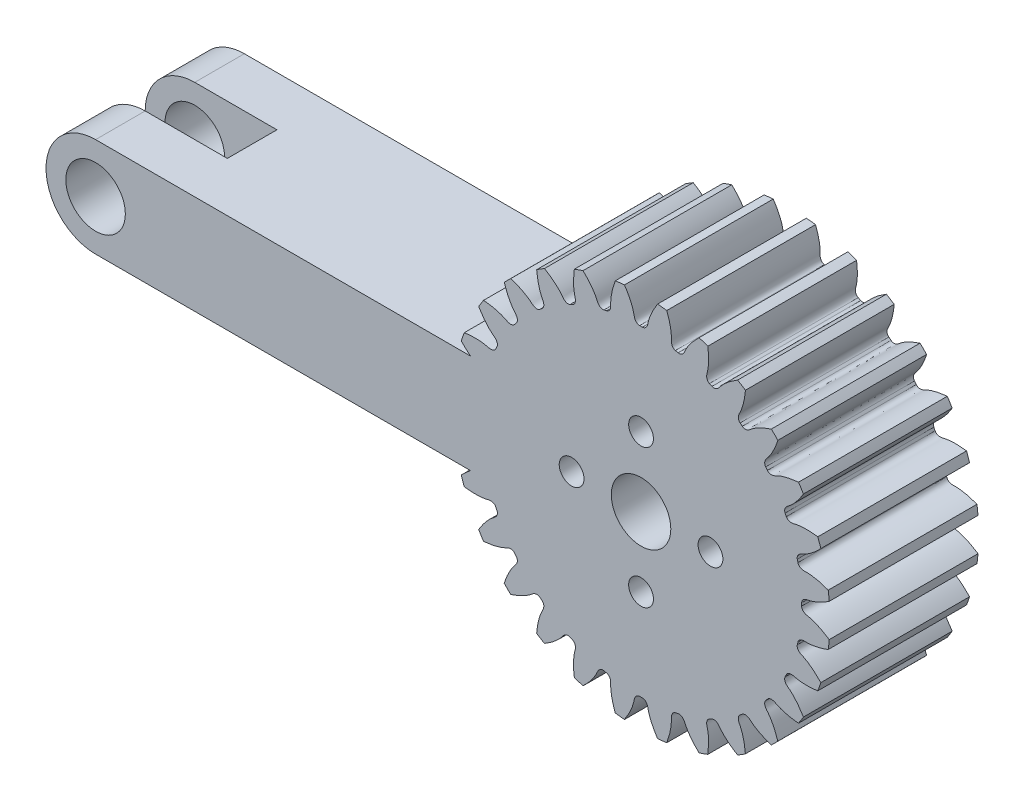
SolidWorks part; units mm, degrees
ref_plane "前视基准面" through (0, 0, 0) normal (0, 0, 1) x (1, 0, 0)
ref_plane "上视基准面" through (0, 0, 0) normal (0, 1, 0) x (1, 0, 0)
ref_plane "右视基准面" through (0, 0, 0) normal (1, 0, 0) x (0, 0, -1)
other "Configuration Table"
sketch "草图1" plane through (0, 0, 0) normal (0, 0, 1) x (1, 0, 0)
  line L4 (-55, -5) -> (-17.1897, -5)
  line L5 (-17.1897, 5) -> (-55, 5)
  circle A0 centre (0, 0) radius 3
  circle A1 centre (-55, 0) radius 3
  arc A104 (-18.1289, -5.8518) -> (-17.8223, -6.7281) centre (0, 0) ccw
  arc A105 (-14.6488, -6.9) -> (-14.528, -7.1508) centre (0, 0) ccw
  arc A106 (-16.3722, -9.7392) -> (-15.8784, -10.5252) centre (0, 0) ccw
  arc A107 (-12.7461, -9.9866) -> (-12.5725, -10.2043) centre (0, 0) ccw
  arc A108 (-13.7946, -13.1382) -> (-13.1382, -13.7946) centre (0, 0) ccw
  arc A109 (-10.2043, -12.5725) -> (-9.9866, -12.7461) centre (0, 0) ccw
  arc A110 (-10.5252, -15.8784) -> (-9.7392, -16.3722) centre (0, 0) ccw
  arc A111 (-7.1508, -14.528) -> (-6.9, -14.6488) centre (0, 0) ccw
  arc A112 (-6.7281, -17.8223) -> (-5.8518, -18.1289) centre (0, 0) ccw
  arc A113 (-3.7388, -15.755) -> (-3.4673, -15.8169) centre (0, 0) ccw
  arc A114 (-2.5935, -18.8726) -> (-1.6711, -18.9766) centre (0, 0) ccw
  arc A115 (-0.1392, -16.1919) -> (0.1392, -16.1919) centre (0, 0) ccw
  arc A116 (1.6711, -18.9766) -> (2.5935, -18.8726) centre (0, 0) ccw
  arc A117 (3.4673, -15.8169) -> (3.7388, -15.755) centre (0, 0) ccw
  arc A118 (5.8518, -18.1289) -> (6.7281, -17.8223) centre (0, 0) ccw
  arc A119 (6.9, -14.6488) -> (7.1508, -14.528) centre (0, 0) ccw
  arc A120 (9.7392, -16.3722) -> (10.5252, -15.8784) centre (0, 0) ccw
  arc A121 (9.9866, -12.7461) -> (10.2043, -12.5725) centre (0, 0) ccw
  arc A122 (13.1382, -13.7946) -> (13.7946, -13.1382) centre (0, 0) ccw
  arc A123 (12.5725, -10.2043) -> (12.7461, -9.9866) centre (0, 0) ccw
  arc A124 (15.8784, -10.5252) -> (16.3722, -9.7392) centre (0, 0) ccw
  arc A125 (14.528, -7.1508) -> (14.6488, -6.9) centre (0, 0) ccw
  arc A126 (17.8223, -6.7281) -> (18.1289, -5.8518) centre (0, 0) ccw
  arc A127 (15.755, -3.7388) -> (15.8169, -3.4673) centre (0, 0) ccw
  arc A128 (18.8726, -2.5935) -> (18.9766, -1.6711) centre (0, 0) ccw
  arc A129 (16.1919, -0.1392) -> (16.1919, 0.1392) centre (0, 0) ccw
  arc A130 (18.9766, 1.6711) -> (18.8726, 2.5935) centre (0, 0) ccw
  arc A131 (15.8169, 3.4673) -> (15.755, 3.7388) centre (0, 0) ccw
  arc A132 (18.1289, 5.8518) -> (17.8223, 6.7281) centre (0, 0) ccw
  arc A133 (14.6488, 6.9) -> (14.528, 7.1508) centre (0, 0) ccw
  arc A134 (16.3722, 9.7392) -> (15.8784, 10.5252) centre (0, 0) ccw
  arc A135 (12.7461, 9.9866) -> (12.5725, 10.2043) centre (0, 0) ccw
  arc A136 (13.7946, 13.1382) -> (13.1382, 13.7946) centre (0, 0) ccw
  arc A137 (10.2043, 12.5725) -> (9.9866, 12.7461) centre (0, 0) ccw
  arc A138 (10.5252, 15.8784) -> (9.7392, 16.3722) centre (0, 0) ccw
  arc A139 (7.1508, 14.528) -> (6.9, 14.6488) centre (0, 0) ccw
  arc A140 (6.7281, 17.8223) -> (5.8518, 18.1289) centre (0, 0) ccw
  arc A141 (3.7388, 15.755) -> (3.4673, 15.8169) centre (0, 0) ccw
  arc A142 (2.5935, 18.8726) -> (1.6711, 18.9766) centre (0, 0) ccw
  arc A143 (0.1392, 16.1919) -> (-0.1392, 16.1919) centre (0, 0) ccw
  arc A144 (-1.6711, 18.9766) -> (-2.5935, 18.8726) centre (0, 0) ccw
  arc A145 (-3.4673, 15.8169) -> (-3.7388, 15.755) centre (0, 0) ccw
  arc A146 (-5.8518, 18.1289) -> (-6.7281, 17.8223) centre (0, 0) ccw
  arc A147 (-6.9, 14.6488) -> (-7.1508, 14.528) centre (0, 0) ccw
  arc A148 (-9.7392, 16.3722) -> (-10.5252, 15.8784) centre (0, 0) ccw
  arc A149 (-9.9866, 12.7461) -> (-10.2043, 12.5725) centre (0, 0) ccw
  arc A150 (-13.1382, 13.7946) -> (-13.7946, 13.1382) centre (0, 0) ccw
  arc A151 (-12.5725, 10.2043) -> (-12.7461, 9.9866) centre (0, 0) ccw
  arc A152 (-15.8784, 10.5252) -> (-16.3722, 9.7392) centre (0, 0) ccw
  arc A153 (-14.528, 7.1508) -> (-14.6488, 6.9) centre (0, 0) ccw
  arc A154 (-17.8223, 6.7281) -> (-18.1289, 5.8518) centre (0, 0) ccw
  arc A155 (-55, 5) -> (-55, -5) centre (-55, 0) ccw
  spline S104 degree 3 poles (-17.1897, -5) (-17.2348, -5.0343) (-17.3497, -5.1242) (-17.5362, -5.2798) (-17.8086, -5.525) (-18.005, -5.7208) (-18.1289, -5.8518) knots 0.59534 0.59534 0.59534 0.59534 0.645252 0.723706 0.808982 0.967655 0.967655 0.967655 0.967655
  spline S105 degree 3 poles (-17.8223, -6.7281) (-17.6438, -6.7532) (-17.3681, -6.7839) (-17.0023, -6.8057) (-16.7348, -6.8117) (-16.4906, -6.808) (-16.2698, -6.7965) (-16.0729, -6.7788) (-15.8998, -6.7568) (-15.7506, -6.7322) (-15.6252, -6.7066) (-15.5335, -6.6846) (-15.4713, -6.6672) (-15.4305, -6.6561) (-15.3936, -6.6472) (-15.3338, -6.6343) (-15.2507, -6.6212) (-15.1426, -6.6153) (-15.0302, -6.6239) (-14.9083, -6.6553) (-14.7624, -6.7338) (-14.6816, -6.8327) (-14.6488, -6.9) knots 0.032345 0.032345 0.032345 0.032345 0.191018 0.276294 0.354748 0.42638 0.49119 0.549178 0.600343 0.644687 0.682208 0.712908 0.727669 0.739016 0.750139 0.761058 0.792861 0.824038 0.856152 0.891705 0.934026 1 1 1 1
  spline S106 degree 3 poles (-14.528, -7.1508) (-14.4959, -7.2184) (-14.4689, -7.3433) (-14.4985, -7.5063) (-14.5499, -7.6211) (-14.6133, -7.7144) (-14.6854, -7.7952) (-14.7474, -7.852) (-14.7948, -7.8908) (-14.8247, -7.9141) (-14.8589, -7.939) (-14.9112, -7.9768) (-14.9856, -8.0348) (-15.0838, -8.1169) (-15.1961, -8.2182) (-15.3212, -8.3398) (-15.4578, -8.4827) (-15.6044, -8.6481) (-15.7595, -8.8368) (-15.9217, -9.0496) (-16.1327, -9.3492) (-16.2806, -9.5839) (-16.3722, -9.7392) knots 0 0 0 0 0.065974 0.108295 0.143848 0.175962 0.207139 0.238942 0.249861 0.260984 0.272331 0.287092 0.317792 0.355313 0.399657 0.450822 0.50881 0.57362 0.645252 0.723706 0.808982 0.967655 0.967655 0.967655 0.967655
  spline S107 degree 3 poles (-15.8784, -10.5252) (-15.6987, -10.51) (-15.4231, -10.4786) (-15.0616, -10.4184) (-14.7995, -10.3647) (-14.5622, -10.3068) (-14.3496, -10.2465) (-14.1615, -10.1854) (-13.9976, -10.1255) (-13.8577, -10.0683) (-13.7411, -10.0154) (-13.6566, -9.9735) (-13.5998, -9.9428) (-13.5625, -9.9228) (-13.5285, -9.9059) (-13.4731, -9.8801) (-13.395, -9.8488) (-13.2909, -9.819) (-13.1794, -9.8023) (-13.0536, -9.8058) (-12.8939, -9.8499) (-12.7931, -9.9284) (-12.7461, -9.9866) knots 0.032345 0.032345 0.032345 0.032345 0.191018 0.276294 0.354748 0.42638 0.49119 0.549178 0.600343 0.644687 0.682208 0.712908 0.727669 0.739016 0.750139 0.761058 0.792861 0.824038 0.856152 0.891705 0.934026 1 1 1 1
  spline S108 degree 3 poles (-12.5725, -10.2043) (-12.5262, -10.2631) (-12.4721, -10.3788) (-12.4647, -10.5443) (-12.4893, -10.6677) (-12.5303, -10.7727) (-12.5826, -10.8676) (-12.6304, -10.9367) (-12.668, -10.9851) (-12.692, -11.0145) (-12.7197, -11.0464) (-12.7623, -11.0949) (-12.822, -11.168) (-12.8994, -11.2698) (-12.9864, -11.3936) (-13.0813, -11.5399) (-13.1826, -11.7097) (-13.2888, -11.9036) (-13.3981, -12.1221) (-13.5087, -12.3656) (-13.6478, -12.7047) (-13.7398, -12.9664) (-13.7946, -13.1382) knots 0 0 0 0 0.065974 0.108295 0.143848 0.175962 0.207139 0.238942 0.249861 0.260984 0.272331 0.287092 0.317792 0.355313 0.399657 0.450822 0.50881 0.57362 0.645252 0.723706 0.808982 0.967655 0.967655 0.967655 0.967655
  spline S109 degree 3 poles (-13.1382, -13.7946) (-12.9664, -13.7398) (-12.7047, -13.6478) (-12.3656, -13.5087) (-12.1221, -13.3981) (-11.9036, -13.2888) (-11.7097, -13.1826) (-11.5399, -13.0813) (-11.3936, -12.9864) (-11.2698, -12.8994) (-11.168, -12.822) (-11.0949, -12.7623) (-11.0464, -12.7197) (-11.0145, -12.692) (-10.9851, -12.668) (-10.9367, -12.6304) (-10.8676, -12.5826) (-10.7727, -12.5303) (-10.6677, -12.4893) (-10.5443, -12.4647) (-10.3788, -12.4721) (-10.2631, -12.5262) (-10.2043, -12.5725) knots 0.032345 0.032345 0.032345 0.032345 0.191018 0.276294 0.354748 0.42638 0.49119 0.549178 0.600343 0.644687 0.682208 0.712908 0.727669 0.739016 0.750139 0.761058 0.792861 0.824038 0.856152 0.891705 0.934026 1 1 1 1
  spline S110 degree 3 poles (-9.9866, -12.7461) (-9.9284, -12.7931) (-9.8499, -12.8939) (-9.8058, -13.0536) (-9.8023, -13.1794) (-9.819, -13.2909) (-9.8488, -13.395) (-9.8801, -13.4731) (-9.9059, -13.5285) (-9.9228, -13.5625) (-9.9428, -13.5998) (-9.9735, -13.6566) (-10.0154, -13.7411) (-10.0683, -13.8577) (-10.1255, -13.9976) (-10.1854, -14.1615) (-10.2465, -14.3496) (-10.3068, -14.5622) (-10.3647, -14.7995) (-10.4184, -15.0616) (-10.4786, -15.4231) (-10.51, -15.6987) (-10.5252, -15.8784) knots 0 0 0 0 0.065974 0.108295 0.143848 0.175962 0.207139 0.238942 0.249861 0.260984 0.272331 0.287092 0.317792 0.355313 0.399657 0.450822 0.50881 0.57362 0.645252 0.723706 0.808982 0.967655 0.967655 0.967655 0.967655
  spline S111 degree 3 poles (-9.7392, -16.3722) (-9.5839, -16.2806) (-9.3492, -16.1327) (-9.0496, -15.9217) (-8.8368, -15.7595) (-8.6481, -15.6044) (-8.4827, -15.4578) (-8.3398, -15.3212) (-8.2182, -15.1961) (-8.1169, -15.0838) (-8.0348, -14.9856) (-7.9768, -14.9112) (-7.939, -14.8589) (-7.9141, -14.8247) (-7.8908, -14.7948) (-7.852, -14.7474) (-7.7952, -14.6854) (-7.7144, -14.6133) (-7.6211, -14.5499) (-7.5063, -14.4985) (-7.3433, -14.4689) (-7.2184, -14.4959) (-7.1508, -14.528) knots 0.032345 0.032345 0.032345 0.032345 0.191018 0.276294 0.354748 0.42638 0.49119 0.549178 0.600343 0.644687 0.682208 0.712908 0.727669 0.739016 0.750139 0.761058 0.792861 0.824038 0.856152 0.891705 0.934026 1 1 1 1
  spline S112 degree 3 poles (-6.9, -14.6488) (-6.8327, -14.6816) (-6.7338, -14.7624) (-6.6553, -14.9083) (-6.6239, -15.0302) (-6.6153, -15.1426) (-6.6212, -15.2507) (-6.6343, -15.3338) (-6.6472, -15.3936) (-6.6561, -15.4305) (-6.6672, -15.4713) (-6.6846, -15.5335) (-6.7066, -15.6252) (-6.7322, -15.7506) (-6.7568, -15.8998) (-6.7788, -16.0729) (-6.7965, -16.2698) (-6.808, -16.4906) (-6.8117, -16.7348) (-6.8057, -17.0023) (-6.7839, -17.3681) (-6.7532, -17.6438) (-6.7281, -17.8223) knots 0 0 0 0 0.065974 0.108295 0.143848 0.175962 0.207139 0.238942 0.249861 0.260984 0.272331 0.287092 0.317792 0.355313 0.399657 0.450822 0.50881 0.57362 0.645252 0.723706 0.808982 0.967655 0.967655 0.967655 0.967655
  spline S113 degree 3 poles (-5.8518, -18.1289) (-5.7208, -18.005) (-5.525, -17.8086) (-5.2798, -17.5362) (-5.1084, -17.3308) (-4.959, -17.1376) (-4.8304, -16.9578) (-4.7214, -16.7928) (-4.6307, -16.6438) (-4.5569, -16.5118) (-4.4987, -16.3978) (-4.4588, -16.3124) (-4.4336, -16.2529) (-4.4168, -16.2141) (-4.4008, -16.1797) (-4.3735, -16.1249) (-4.332, -16.0518) (-4.2692, -15.9635) (-4.1924, -15.881) (-4.0919, -15.8053) (-3.9395, -15.7401) (-3.8118, -15.7387) (-3.7388, -15.755) knots 0.032345 0.032345 0.032345 0.032345 0.191018 0.276294 0.354748 0.42638 0.49119 0.549178 0.600343 0.644687 0.682208 0.712908 0.727669 0.739016 0.750139 0.761058 0.792861 0.824038 0.856152 0.891705 0.934026 1 1 1 1
  spline S114 degree 3 poles (-3.4673, -15.8169) (-3.3945, -15.8339) (-3.28, -15.8907) (-3.171, -16.0155) (-3.1133, -16.1273) (-3.0799, -16.235) (-3.0616, -16.3417) (-3.0559, -16.4256) (-3.0551, -16.4868) (-3.0556, -16.5248) (-3.0574, -16.567) (-3.0604, -16.6315) (-3.0615, -16.7259) (-3.0586, -16.8538) (-3.0494, -17.0047) (-3.0323, -17.1783) (-3.0057, -17.3743) (-2.9678, -17.592) (-2.917, -17.831) (-2.8517, -18.0904) (-2.749, -18.4422) (-2.6578, -18.7041) (-2.5935, -18.8726) knots 0 0 0 0 0.065974 0.108295 0.143848 0.175962 0.207139 0.238942 0.249861 0.260984 0.272331 0.287092 0.317792 0.355313 0.399657 0.450822 0.50881 0.57362 0.645252 0.723706 0.808982 0.967655 0.967655 0.967655 0.967655
  spline S115 degree 3 poles (-1.6711, -18.9766) (-1.5709, -18.8266) (-1.4237, -18.5915) (-1.2453, -18.2714) (-1.1239, -18.033) (-1.0212, -17.8114) (-0.9358, -17.6075) (-0.8662, -17.4224) (-0.811, -17.2569) (-0.7684, -17.1118) (-0.7371, -16.9878) (-0.7172, -16.8956) (-0.7058, -16.832) (-0.6981, -16.7904) (-0.6901, -16.7533) (-0.6758, -16.6938) (-0.6515, -16.6133) (-0.6099, -16.5133) (-0.5534, -16.4157) (-0.4723, -16.3196) (-0.3383, -16.2221) (-0.214, -16.1923) (-0.1392, -16.1919) knots 0.032345 0.032345 0.032345 0.032345 0.191018 0.276294 0.354748 0.42638 0.49119 0.549178 0.600343 0.644687 0.682208 0.712908 0.727669 0.739016 0.750139 0.761058 0.792861 0.824038 0.856152 0.891705 0.934026 1 1 1 1
  spline S116 degree 3 poles (0.1392, -16.1919) (0.214, -16.1923) (0.3383, -16.2221) (0.4723, -16.3196) (0.5534, -16.4157) (0.6099, -16.5133) (0.6515, -16.6133) (0.6758, -16.6938) (0.6901, -16.7533) (0.6981, -16.7904) (0.7058, -16.832) (0.7172, -16.8956) (0.7371, -16.9878) (0.7684, -17.1118) (0.811, -17.2569) (0.8662, -17.4224) (0.9358, -17.6075) (1.0212, -17.8114) (1.1239, -18.033) (1.2453, -18.2714) (1.4237, -18.5915) (1.5709, -18.8266) (1.6711, -18.9766) knots 0 0 0 0 0.065974 0.108295 0.143848 0.175962 0.207139 0.238942 0.249861 0.260984 0.272331 0.287092 0.317792 0.355313 0.399657 0.450822 0.50881 0.57362 0.645252 0.723706 0.808982 0.967655 0.967655 0.967655 0.967655
  spline S117 degree 3 poles (2.5935, -18.8726) (2.6578, -18.7041) (2.749, -18.4422) (2.8517, -18.0904) (2.917, -17.831) (2.9678, -17.592) (3.0057, -17.3743) (3.0323, -17.1783) (3.0494, -17.0047) (3.0586, -16.8538) (3.0615, -16.7259) (3.0604, -16.6315) (3.0574, -16.567) (3.0556, -16.5248) (3.0551, -16.4868) (3.0559, -16.4256) (3.0616, -16.3417) (3.0799, -16.235) (3.1133, -16.1273) (3.171, -16.0155) (3.28, -15.8907) (3.3945, -15.8339) (3.4673, -15.8169) knots 0.032345 0.032345 0.032345 0.032345 0.191018 0.276294 0.354748 0.42638 0.49119 0.549178 0.600343 0.644687 0.682208 0.712908 0.727669 0.739016 0.750139 0.761058 0.792861 0.824038 0.856152 0.891705 0.934026 1 1 1 1
  spline S118 degree 3 poles (3.7388, -15.755) (3.8118, -15.7387) (3.9395, -15.7401) (4.0919, -15.8053) (4.1924, -15.881) (4.2692, -15.9635) (4.332, -16.0518) (4.3735, -16.1249) (4.4008, -16.1797) (4.4168, -16.2141) (4.4336, -16.2529) (4.4588, -16.3124) (4.4987, -16.3978) (4.5569, -16.5118) (4.6307, -16.6438) (4.7214, -16.7928) (4.8304, -16.9578) (4.959, -17.1376) (5.1084, -17.3308) (5.2798, -17.5362) (5.525, -17.8086) (5.7208, -18.005) (5.8518, -18.1289) knots 0 0 0 0 0.065974 0.108295 0.143848 0.175962 0.207139 0.238942 0.249861 0.260984 0.272331 0.287092 0.317792 0.355313 0.399657 0.450822 0.50881 0.57362 0.645252 0.723706 0.808982 0.967655 0.967655 0.967655 0.967655
  spline S119 degree 3 poles (6.7281, -17.8223) (6.7532, -17.6438) (6.7839, -17.3681) (6.8057, -17.0023) (6.8117, -16.7348) (6.808, -16.4906) (6.7965, -16.2698) (6.7788, -16.0729) (6.7568, -15.8998) (6.7322, -15.7506) (6.7066, -15.6252) (6.6846, -15.5335) (6.6672, -15.4713) (6.6561, -15.4305) (6.6472, -15.3936) (6.6343, -15.3338) (6.6212, -15.2507) (6.6153, -15.1426) (6.6239, -15.0302) (6.6553, -14.9083) (6.7338, -14.7624) (6.8327, -14.6816) (6.9, -14.6488) knots 0.032345 0.032345 0.032345 0.032345 0.191018 0.276294 0.354748 0.42638 0.49119 0.549178 0.600343 0.644687 0.682208 0.712908 0.727669 0.739016 0.750139 0.761058 0.792861 0.824038 0.856152 0.891705 0.934026 1 1 1 1
  spline S120 degree 3 poles (7.1508, -14.528) (7.2184, -14.4959) (7.3433, -14.4689) (7.5063, -14.4985) (7.6211, -14.5499) (7.7144, -14.6133) (7.7952, -14.6854) (7.852, -14.7474) (7.8908, -14.7948) (7.9141, -14.8247) (7.939, -14.8589) (7.9768, -14.9112) (8.0348, -14.9856) (8.1169, -15.0838) (8.2182, -15.1961) (8.3398, -15.3212) (8.4827, -15.4578) (8.6481, -15.6044) (8.8368, -15.7595) (9.0496, -15.9217) (9.3492, -16.1327) (9.5839, -16.2806) (9.7392, -16.3722) knots 0 0 0 0 0.065974 0.108295 0.143848 0.175962 0.207139 0.238942 0.249861 0.260984 0.272331 0.287092 0.317792 0.355313 0.399657 0.450822 0.50881 0.57362 0.645252 0.723706 0.808982 0.967655 0.967655 0.967655 0.967655
  spline S121 degree 3 poles (10.5252, -15.8784) (10.51, -15.6987) (10.4786, -15.4231) (10.4184, -15.0616) (10.3647, -14.7995) (10.3068, -14.5622) (10.2465, -14.3496) (10.1854, -14.1615) (10.1255, -13.9976) (10.0683, -13.8577) (10.0154, -13.7411) (9.9735, -13.6566) (9.9428, -13.5998) (9.9228, -13.5625) (9.9059, -13.5285) (9.8801, -13.4731) (9.8488, -13.395) (9.819, -13.2909) (9.8023, -13.1794) (9.8058, -13.0536) (9.8499, -12.8939) (9.9284, -12.7931) (9.9866, -12.7461) knots 0.032345 0.032345 0.032345 0.032345 0.191018 0.276294 0.354748 0.42638 0.49119 0.549178 0.600343 0.644687 0.682208 0.712908 0.727669 0.739016 0.750139 0.761058 0.792861 0.824038 0.856152 0.891705 0.934026 1 1 1 1
  spline S122 degree 3 poles (10.2043, -12.5725) (10.2631, -12.5262) (10.3788, -12.4721) (10.5443, -12.4647) (10.6677, -12.4893) (10.7727, -12.5303) (10.8676, -12.5826) (10.9367, -12.6304) (10.9851, -12.668) (11.0145, -12.692) (11.0464, -12.7197) (11.0949, -12.7623) (11.168, -12.822) (11.2698, -12.8994) (11.3936, -12.9864) (11.5399, -13.0813) (11.7097, -13.1826) (11.9036, -13.2888) (12.1221, -13.3981) (12.3656, -13.5087) (12.7047, -13.6478) (12.9664, -13.7398) (13.1382, -13.7946) knots 0 0 0 0 0.065974 0.108295 0.143848 0.175962 0.207139 0.238942 0.249861 0.260984 0.272331 0.287092 0.317792 0.355313 0.399657 0.450822 0.50881 0.57362 0.645252 0.723706 0.808982 0.967655 0.967655 0.967655 0.967655
  spline S123 degree 3 poles (13.7946, -13.1382) (13.7398, -12.9664) (13.6478, -12.7047) (13.5087, -12.3656) (13.3981, -12.1221) (13.2888, -11.9036) (13.1826, -11.7097) (13.0813, -11.5399) (12.9864, -11.3936) (12.8994, -11.2698) (12.822, -11.168) (12.7623, -11.0949) (12.7197, -11.0464) (12.692, -11.0145) (12.668, -10.9851) (12.6304, -10.9367) (12.5826, -10.8676) (12.5303, -10.7727) (12.4893, -10.6677) (12.4647, -10.5443) (12.4721, -10.3788) (12.5262, -10.2631) (12.5725, -10.2043) knots 0.032345 0.032345 0.032345 0.032345 0.191018 0.276294 0.354748 0.42638 0.49119 0.549178 0.600343 0.644687 0.682208 0.712908 0.727669 0.739016 0.750139 0.761058 0.792861 0.824038 0.856152 0.891705 0.934026 1 1 1 1
  spline S124 degree 3 poles (12.7461, -9.9866) (12.7931, -9.9284) (12.8939, -9.8499) (13.0536, -9.8058) (13.1794, -9.8023) (13.2909, -9.819) (13.395, -9.8488) (13.4731, -9.8801) (13.5285, -9.9059) (13.5625, -9.9228) (13.5998, -9.9428) (13.6566, -9.9735) (13.7411, -10.0154) (13.8577, -10.0683) (13.9976, -10.1255) (14.1615, -10.1854) (14.3496, -10.2465) (14.5622, -10.3068) (14.7995, -10.3647) (15.0616, -10.4184) (15.4231, -10.4786) (15.6987, -10.51) (15.8784, -10.5252) knots 0 0 0 0 0.065974 0.108295 0.143848 0.175962 0.207139 0.238942 0.249861 0.260984 0.272331 0.287092 0.317792 0.355313 0.399657 0.450822 0.50881 0.57362 0.645252 0.723706 0.808982 0.967655 0.967655 0.967655 0.967655
  spline S125 degree 3 poles (16.3722, -9.7392) (16.2806, -9.5839) (16.1327, -9.3492) (15.9217, -9.0496) (15.7595, -8.8368) (15.6044, -8.6481) (15.4578, -8.4827) (15.3212, -8.3398) (15.1961, -8.2182) (15.0838, -8.1169) (14.9856, -8.0348) (14.9112, -7.9768) (14.8589, -7.939) (14.8247, -7.9141) (14.7948, -7.8908) (14.7474, -7.852) (14.6854, -7.7952) (14.6133, -7.7144) (14.5499, -7.6211) (14.4985, -7.5063) (14.4689, -7.3433) (14.4959, -7.2184) (14.528, -7.1508) knots 0.032345 0.032345 0.032345 0.032345 0.191018 0.276294 0.354748 0.42638 0.49119 0.549178 0.600343 0.644687 0.682208 0.712908 0.727669 0.739016 0.750139 0.761058 0.792861 0.824038 0.856152 0.891705 0.934026 1 1 1 1
  spline S126 degree 3 poles (14.6488, -6.9) (14.6816, -6.8327) (14.7624, -6.7338) (14.9083, -6.6553) (15.0302, -6.6239) (15.1426, -6.6153) (15.2507, -6.6212) (15.3338, -6.6343) (15.3936, -6.6472) (15.4305, -6.6561) (15.4713, -6.6672) (15.5335, -6.6846) (15.6252, -6.7066) (15.7506, -6.7322) (15.8998, -6.7568) (16.0729, -6.7788) (16.2698, -6.7965) (16.4906, -6.808) (16.7348, -6.8117) (17.0023, -6.8057) (17.3681, -6.7839) (17.6438, -6.7532) (17.8223, -6.7281) knots 0 0 0 0 0.065974 0.108295 0.143848 0.175962 0.207139 0.238942 0.249861 0.260984 0.272331 0.287092 0.317792 0.355313 0.399657 0.450822 0.50881 0.57362 0.645252 0.723706 0.808982 0.967655 0.967655 0.967655 0.967655
  spline S127 degree 3 poles (18.1289, -5.8518) (18.005, -5.7208) (17.8086, -5.525) (17.5362, -5.2798) (17.3308, -5.1084) (17.1376, -4.959) (16.9578, -4.8304) (16.7928, -4.7214) (16.6438, -4.6307) (16.5118, -4.5569) (16.3978, -4.4987) (16.3124, -4.4588) (16.2529, -4.4336) (16.2141, -4.4168) (16.1797, -4.4008) (16.1249, -4.3735) (16.0518, -4.332) (15.9635, -4.2692) (15.881, -4.1924) (15.8053, -4.0919) (15.7401, -3.9395) (15.7387, -3.8118) (15.755, -3.7388) knots 0.032345 0.032345 0.032345 0.032345 0.191018 0.276294 0.354748 0.42638 0.49119 0.549178 0.600343 0.644687 0.682208 0.712908 0.727669 0.739016 0.750139 0.761058 0.792861 0.824038 0.856152 0.891705 0.934026 1 1 1 1
  spline S128 degree 3 poles (15.8169, -3.4673) (15.8339, -3.3945) (15.8907, -3.28) (16.0155, -3.171) (16.1273, -3.1133) (16.235, -3.0799) (16.3417, -3.0616) (16.4256, -3.0559) (16.4868, -3.0551) (16.5248, -3.0556) (16.567, -3.0574) (16.6315, -3.0604) (16.7259, -3.0615) (16.8538, -3.0586) (17.0047, -3.0494) (17.1783, -3.0323) (17.3743, -3.0057) (17.592, -2.9678) (17.831, -2.917) (18.0904, -2.8517) (18.4422, -2.749) (18.7041, -2.6578) (18.8726, -2.5935) knots 0 0 0 0 0.065974 0.108295 0.143848 0.175962 0.207139 0.238942 0.249861 0.260984 0.272331 0.287092 0.317792 0.355313 0.399657 0.450822 0.50881 0.57362 0.645252 0.723706 0.808982 0.967655 0.967655 0.967655 0.967655
  spline S129 degree 3 poles (18.9766, -1.6711) (18.8266, -1.5709) (18.5915, -1.4237) (18.2714, -1.2453) (18.033, -1.1239) (17.8114, -1.0212) (17.6075, -0.9358) (17.4224, -0.8662) (17.2569, -0.811) (17.1118, -0.7684) (16.9878, -0.7371) (16.8956, -0.7172) (16.832, -0.7058) (16.7904, -0.6981) (16.7533, -0.6901) (16.6938, -0.6758) (16.6133, -0.6515) (16.5133, -0.6099) (16.4157, -0.5534) (16.3196, -0.4723) (16.2221, -0.3383) (16.1923, -0.214) (16.1919, -0.1392) knots 0.032345 0.032345 0.032345 0.032345 0.191018 0.276294 0.354748 0.42638 0.49119 0.549178 0.600343 0.644687 0.682208 0.712908 0.727669 0.739016 0.750139 0.761058 0.792861 0.824038 0.856152 0.891705 0.934026 1 1 1 1
  spline S130 degree 3 poles (16.1919, 0.1392) (16.1923, 0.214) (16.2221, 0.3383) (16.3196, 0.4723) (16.4157, 0.5534) (16.5133, 0.6099) (16.6133, 0.6515) (16.6938, 0.6758) (16.7533, 0.6901) (16.7904, 0.6981) (16.832, 0.7058) (16.8956, 0.7172) (16.9878, 0.7371) (17.1118, 0.7684) (17.2569, 0.811) (17.4224, 0.8662) (17.6075, 0.9358) (17.8114, 1.0212) (18.033, 1.1239) (18.2714, 1.2453) (18.5915, 1.4237) (18.8266, 1.5709) (18.9766, 1.6711) knots 0 0 0 0 0.065974 0.108295 0.143848 0.175962 0.207139 0.238942 0.249861 0.260984 0.272331 0.287092 0.317792 0.355313 0.399657 0.450822 0.50881 0.57362 0.645252 0.723706 0.808982 0.967655 0.967655 0.967655 0.967655
  spline S131 degree 3 poles (18.8726, 2.5935) (18.7041, 2.6578) (18.4422, 2.749) (18.0904, 2.8517) (17.831, 2.917) (17.592, 2.9678) (17.3743, 3.0057) (17.1783, 3.0323) (17.0047, 3.0494) (16.8538, 3.0586) (16.7259, 3.0615) (16.6315, 3.0604) (16.567, 3.0574) (16.5248, 3.0556) (16.4868, 3.0551) (16.4256, 3.0559) (16.3417, 3.0616) (16.235, 3.0799) (16.1273, 3.1133) (16.0155, 3.171) (15.8907, 3.28) (15.8339, 3.3945) (15.8169, 3.4673) knots 0.032345 0.032345 0.032345 0.032345 0.191018 0.276294 0.354748 0.42638 0.49119 0.549178 0.600343 0.644687 0.682208 0.712908 0.727669 0.739016 0.750139 0.761058 0.792861 0.824038 0.856152 0.891705 0.934026 1 1 1 1
  spline S132 degree 3 poles (15.755, 3.7388) (15.7387, 3.8118) (15.7401, 3.9395) (15.8053, 4.0919) (15.881, 4.1924) (15.9635, 4.2692) (16.0518, 4.332) (16.1249, 4.3735) (16.1797, 4.4008) (16.2141, 4.4168) (16.2529, 4.4336) (16.3124, 4.4588) (16.3978, 4.4987) (16.5118, 4.5569) (16.6438, 4.6307) (16.7928, 4.7214) (16.9578, 4.8304) (17.1376, 4.959) (17.3308, 5.1084) (17.5362, 5.2798) (17.8086, 5.525) (18.005, 5.7208) (18.1289, 5.8518) knots 0 0 0 0 0.065974 0.108295 0.143848 0.175962 0.207139 0.238942 0.249861 0.260984 0.272331 0.287092 0.317792 0.355313 0.399657 0.450822 0.50881 0.57362 0.645252 0.723706 0.808982 0.967655 0.967655 0.967655 0.967655
  spline S133 degree 3 poles (17.8223, 6.7281) (17.6438, 6.7532) (17.3681, 6.7839) (17.0023, 6.8057) (16.7348, 6.8117) (16.4906, 6.808) (16.2698, 6.7965) (16.0729, 6.7788) (15.8998, 6.7568) (15.7506, 6.7322) (15.6252, 6.7066) (15.5335, 6.6846) (15.4713, 6.6672) (15.4305, 6.6561) (15.3936, 6.6472) (15.3338, 6.6343) (15.2507, 6.6212) (15.1426, 6.6153) (15.0302, 6.6239) (14.9083, 6.6553) (14.7624, 6.7338) (14.6816, 6.8327) (14.6488, 6.9) knots 0.032345 0.032345 0.032345 0.032345 0.191018 0.276294 0.354748 0.42638 0.49119 0.549178 0.600343 0.644687 0.682208 0.712908 0.727669 0.739016 0.750139 0.761058 0.792861 0.824038 0.856152 0.891705 0.934026 1 1 1 1
  spline S134 degree 3 poles (14.528, 7.1508) (14.4959, 7.2184) (14.4689, 7.3433) (14.4985, 7.5063) (14.5499, 7.6211) (14.6133, 7.7144) (14.6854, 7.7952) (14.7474, 7.852) (14.7948, 7.8908) (14.8247, 7.9141) (14.8589, 7.939) (14.9112, 7.9768) (14.9856, 8.0348) (15.0838, 8.1169) (15.1961, 8.2182) (15.3212, 8.3398) (15.4578, 8.4827) (15.6044, 8.6481) (15.7595, 8.8368) (15.9217, 9.0496) (16.1327, 9.3492) (16.2806, 9.5839) (16.3722, 9.7392) knots 0 0 0 0 0.065974 0.108295 0.143848 0.175962 0.207139 0.238942 0.249861 0.260984 0.272331 0.287092 0.317792 0.355313 0.399657 0.450822 0.50881 0.57362 0.645252 0.723706 0.808982 0.967655 0.967655 0.967655 0.967655
  spline S135 degree 3 poles (15.8784, 10.5252) (15.6987, 10.51) (15.4231, 10.4786) (15.0616, 10.4184) (14.7995, 10.3647) (14.5622, 10.3068) (14.3496, 10.2465) (14.1615, 10.1854) (13.9976, 10.1255) (13.8577, 10.0683) (13.7411, 10.0154) (13.6566, 9.9735) (13.5998, 9.9428) (13.5625, 9.9228) (13.5285, 9.9059) (13.4731, 9.8801) (13.395, 9.8488) (13.2909, 9.819) (13.1794, 9.8023) (13.0536, 9.8058) (12.8939, 9.8499) (12.7931, 9.9284) (12.7461, 9.9866) knots 0.032345 0.032345 0.032345 0.032345 0.191018 0.276294 0.354748 0.42638 0.49119 0.549178 0.600343 0.644687 0.682208 0.712908 0.727669 0.739016 0.750139 0.761058 0.792861 0.824038 0.856152 0.891705 0.934026 1 1 1 1
  spline S136 degree 3 poles (12.5725, 10.2043) (12.5262, 10.2631) (12.4721, 10.3788) (12.4647, 10.5443) (12.4893, 10.6677) (12.5303, 10.7727) (12.5826, 10.8676) (12.6304, 10.9367) (12.668, 10.9851) (12.692, 11.0145) (12.7197, 11.0464) (12.7623, 11.0949) (12.822, 11.168) (12.8994, 11.2698) (12.9864, 11.3936) (13.0813, 11.5399) (13.1826, 11.7097) (13.2888, 11.9036) (13.3981, 12.1221) (13.5087, 12.3656) (13.6478, 12.7047) (13.7398, 12.9664) (13.7946, 13.1382) knots 0 0 0 0 0.065974 0.108295 0.143848 0.175962 0.207139 0.238942 0.249861 0.260984 0.272331 0.287092 0.317792 0.355313 0.399657 0.450822 0.50881 0.57362 0.645252 0.723706 0.808982 0.967655 0.967655 0.967655 0.967655
  spline S137 degree 3 poles (13.1382, 13.7946) (12.9664, 13.7398) (12.7047, 13.6478) (12.3656, 13.5087) (12.1221, 13.3981) (11.9036, 13.2888) (11.7097, 13.1826) (11.5399, 13.0813) (11.3936, 12.9864) (11.2698, 12.8994) (11.168, 12.822) (11.0949, 12.7623) (11.0464, 12.7197) (11.0145, 12.692) (10.9851, 12.668) (10.9367, 12.6304) (10.8676, 12.5826) (10.7727, 12.5303) (10.6677, 12.4893) (10.5443, 12.4647) (10.3788, 12.4721) (10.2631, 12.5262) (10.2043, 12.5725) knots 0.032345 0.032345 0.032345 0.032345 0.191018 0.276294 0.354748 0.42638 0.49119 0.549178 0.600343 0.644687 0.682208 0.712908 0.727669 0.739016 0.750139 0.761058 0.792861 0.824038 0.856152 0.891705 0.934026 1 1 1 1
  spline S138 degree 3 poles (9.9866, 12.7461) (9.9284, 12.7931) (9.8499, 12.8939) (9.8058, 13.0536) (9.8023, 13.1794) (9.819, 13.2909) (9.8488, 13.395) (9.8801, 13.4731) (9.9059, 13.5285) (9.9228, 13.5625) (9.9428, 13.5998) (9.9735, 13.6566) (10.0154, 13.7411) (10.0683, 13.8577) (10.1255, 13.9976) (10.1854, 14.1615) (10.2465, 14.3496) (10.3068, 14.5622) (10.3647, 14.7995) (10.4184, 15.0616) (10.4786, 15.4231) (10.51, 15.6987) (10.5252, 15.8784) knots 0 0 0 0 0.065974 0.108295 0.143848 0.175962 0.207139 0.238942 0.249861 0.260984 0.272331 0.287092 0.317792 0.355313 0.399657 0.450822 0.50881 0.57362 0.645252 0.723706 0.808982 0.967655 0.967655 0.967655 0.967655
  spline S139 degree 3 poles (9.7392, 16.3722) (9.5839, 16.2806) (9.3492, 16.1327) (9.0496, 15.9217) (8.8368, 15.7595) (8.6481, 15.6044) (8.4827, 15.4578) (8.3398, 15.3212) (8.2182, 15.1961) (8.1169, 15.0838) (8.0348, 14.9856) (7.9768, 14.9112) (7.939, 14.8589) (7.9141, 14.8247) (7.8908, 14.7948) (7.852, 14.7474) (7.7952, 14.6854) (7.7144, 14.6133) (7.6211, 14.5499) (7.5063, 14.4985) (7.3433, 14.4689) (7.2184, 14.4959) (7.1508, 14.528) knots 0.032345 0.032345 0.032345 0.032345 0.191018 0.276294 0.354748 0.42638 0.49119 0.549178 0.600343 0.644687 0.682208 0.712908 0.727669 0.739016 0.750139 0.761058 0.792861 0.824038 0.856152 0.891705 0.934026 1 1 1 1
  spline S140 degree 3 poles (6.9, 14.6488) (6.8327, 14.6816) (6.7338, 14.7624) (6.6553, 14.9083) (6.6239, 15.0302) (6.6153, 15.1426) (6.6212, 15.2507) (6.6343, 15.3338) (6.6472, 15.3936) (6.6561, 15.4305) (6.6672, 15.4713) (6.6846, 15.5335) (6.7066, 15.6252) (6.7322, 15.7506) (6.7568, 15.8998) (6.7788, 16.0729) (6.7965, 16.2698) (6.808, 16.4906) (6.8117, 16.7348) (6.8057, 17.0023) (6.7839, 17.3681) (6.7532, 17.6438) (6.7281, 17.8223) knots 0 0 0 0 0.065974 0.108295 0.143848 0.175962 0.207139 0.238942 0.249861 0.260984 0.272331 0.287092 0.317792 0.355313 0.399657 0.450822 0.50881 0.57362 0.645252 0.723706 0.808982 0.967655 0.967655 0.967655 0.967655
  spline S141 degree 3 poles (5.8518, 18.1289) (5.7208, 18.005) (5.525, 17.8086) (5.2798, 17.5362) (5.1084, 17.3308) (4.959, 17.1376) (4.8304, 16.9578) (4.7214, 16.7928) (4.6307, 16.6438) (4.5569, 16.5118) (4.4987, 16.3978) (4.4588, 16.3124) (4.4336, 16.2529) (4.4168, 16.2141) (4.4008, 16.1797) (4.3735, 16.1249) (4.332, 16.0518) (4.2692, 15.9635) (4.1924, 15.881) (4.0919, 15.8053) (3.9395, 15.7401) (3.8118, 15.7387) (3.7388, 15.755) knots 0.032345 0.032345 0.032345 0.032345 0.191018 0.276294 0.354748 0.42638 0.49119 0.549178 0.600343 0.644687 0.682208 0.712908 0.727669 0.739016 0.750139 0.761058 0.792861 0.824038 0.856152 0.891705 0.934026 1 1 1 1
  spline S142 degree 3 poles (3.4673, 15.8169) (3.3945, 15.8339) (3.28, 15.8907) (3.171, 16.0155) (3.1133, 16.1273) (3.0799, 16.235) (3.0616, 16.3417) (3.0559, 16.4256) (3.0551, 16.4868) (3.0556, 16.5248) (3.0574, 16.567) (3.0604, 16.6315) (3.0615, 16.7259) (3.0586, 16.8538) (3.0494, 17.0047) (3.0323, 17.1783) (3.0057, 17.3743) (2.9678, 17.592) (2.917, 17.831) (2.8517, 18.0904) (2.749, 18.4422) (2.6578, 18.7041) (2.5935, 18.8726) knots 0 0 0 0 0.065974 0.108295 0.143848 0.175962 0.207139 0.238942 0.249861 0.260984 0.272331 0.287092 0.317792 0.355313 0.399657 0.450822 0.50881 0.57362 0.645252 0.723706 0.808982 0.967655 0.967655 0.967655 0.967655
  spline S143 degree 3 poles (1.6711, 18.9766) (1.5709, 18.8266) (1.4237, 18.5915) (1.2453, 18.2714) (1.1239, 18.033) (1.0212, 17.8114) (0.9358, 17.6075) (0.8662, 17.4224) (0.811, 17.2569) (0.7684, 17.1118) (0.7371, 16.9878) (0.7172, 16.8956) (0.7058, 16.832) (0.6981, 16.7904) (0.6901, 16.7533) (0.6758, 16.6938) (0.6515, 16.6133) (0.6099, 16.5133) (0.5534, 16.4157) (0.4723, 16.3196) (0.3383, 16.2221) (0.214, 16.1923) (0.1392, 16.1919) knots 0.032345 0.032345 0.032345 0.032345 0.191018 0.276294 0.354748 0.42638 0.49119 0.549178 0.600343 0.644687 0.682208 0.712908 0.727669 0.739016 0.750139 0.761058 0.792861 0.824038 0.856152 0.891705 0.934026 1 1 1 1
  spline S144 degree 3 poles (-0.1392, 16.1919) (-0.214, 16.1923) (-0.3383, 16.2221) (-0.4723, 16.3196) (-0.5534, 16.4157) (-0.6099, 16.5133) (-0.6515, 16.6133) (-0.6758, 16.6938) (-0.6901, 16.7533) (-0.6981, 16.7904) (-0.7058, 16.832) (-0.7172, 16.8956) (-0.7371, 16.9878) (-0.7684, 17.1118) (-0.811, 17.2569) (-0.8662, 17.4224) (-0.9358, 17.6075) (-1.0212, 17.8114) (-1.1239, 18.033) (-1.2453, 18.2714) (-1.4237, 18.5915) (-1.5709, 18.8266) (-1.6711, 18.9766) knots 0 0 0 0 0.065974 0.108295 0.143848 0.175962 0.207139 0.238942 0.249861 0.260984 0.272331 0.287092 0.317792 0.355313 0.399657 0.450822 0.50881 0.57362 0.645252 0.723706 0.808982 0.967655 0.967655 0.967655 0.967655
  spline S145 degree 3 poles (-2.5935, 18.8726) (-2.6578, 18.7041) (-2.749, 18.4422) (-2.8517, 18.0904) (-2.917, 17.831) (-2.9678, 17.592) (-3.0057, 17.3743) (-3.0323, 17.1783) (-3.0494, 17.0047) (-3.0586, 16.8538) (-3.0615, 16.7259) (-3.0604, 16.6315) (-3.0574, 16.567) (-3.0556, 16.5248) (-3.0551, 16.4868) (-3.0559, 16.4256) (-3.0616, 16.3417) (-3.0799, 16.235) (-3.1133, 16.1273) (-3.171, 16.0155) (-3.28, 15.8907) (-3.3945, 15.8339) (-3.4673, 15.8169) knots 0.032345 0.032345 0.032345 0.032345 0.191018 0.276294 0.354748 0.42638 0.49119 0.549178 0.600343 0.644687 0.682208 0.712908 0.727669 0.739016 0.750139 0.761058 0.792861 0.824038 0.856152 0.891705 0.934026 1 1 1 1
  spline S146 degree 3 poles (-3.7388, 15.755) (-3.8118, 15.7387) (-3.9395, 15.7401) (-4.0919, 15.8053) (-4.1924, 15.881) (-4.2692, 15.9635) (-4.332, 16.0518) (-4.3735, 16.1249) (-4.4008, 16.1797) (-4.4168, 16.2141) (-4.4336, 16.2529) (-4.4588, 16.3124) (-4.4987, 16.3978) (-4.5569, 16.5118) (-4.6307, 16.6438) (-4.7214, 16.7928) (-4.8304, 16.9578) (-4.959, 17.1376) (-5.1084, 17.3308) (-5.2798, 17.5362) (-5.525, 17.8086) (-5.7208, 18.005) (-5.8518, 18.1289) knots 0 0 0 0 0.065974 0.108295 0.143848 0.175962 0.207139 0.238942 0.249861 0.260984 0.272331 0.287092 0.317792 0.355313 0.399657 0.450822 0.50881 0.57362 0.645252 0.723706 0.808982 0.967655 0.967655 0.967655 0.967655
  spline S147 degree 3 poles (-6.7281, 17.8223) (-6.7532, 17.6438) (-6.7839, 17.3681) (-6.8057, 17.0023) (-6.8117, 16.7348) (-6.808, 16.4906) (-6.7965, 16.2698) (-6.7788, 16.0729) (-6.7568, 15.8998) (-6.7322, 15.7506) (-6.7066, 15.6252) (-6.6846, 15.5335) (-6.6672, 15.4713) (-6.6561, 15.4305) (-6.6472, 15.3936) (-6.6343, 15.3338) (-6.6212, 15.2507) (-6.6153, 15.1426) (-6.6239, 15.0302) (-6.6553, 14.9083) (-6.7338, 14.7624) (-6.8327, 14.6816) (-6.9, 14.6488) knots 0.032345 0.032345 0.032345 0.032345 0.191018 0.276294 0.354748 0.42638 0.49119 0.549178 0.600343 0.644687 0.682208 0.712908 0.727669 0.739016 0.750139 0.761058 0.792861 0.824038 0.856152 0.891705 0.934026 1 1 1 1
  spline S148 degree 3 poles (-7.1508, 14.528) (-7.2184, 14.4959) (-7.3433, 14.4689) (-7.5063, 14.4985) (-7.6211, 14.5499) (-7.7144, 14.6133) (-7.7952, 14.6854) (-7.852, 14.7474) (-7.8908, 14.7948) (-7.9141, 14.8247) (-7.939, 14.8589) (-7.9768, 14.9112) (-8.0348, 14.9856) (-8.1169, 15.0838) (-8.2182, 15.1961) (-8.3398, 15.3212) (-8.4827, 15.4578) (-8.6481, 15.6044) (-8.8368, 15.7595) (-9.0496, 15.9217) (-9.3492, 16.1327) (-9.5839, 16.2806) (-9.7392, 16.3722) knots 0 0 0 0 0.065974 0.108295 0.143848 0.175962 0.207139 0.238942 0.249861 0.260984 0.272331 0.287092 0.317792 0.355313 0.399657 0.450822 0.50881 0.57362 0.645252 0.723706 0.808982 0.967655 0.967655 0.967655 0.967655
  spline S149 degree 3 poles (-10.5252, 15.8784) (-10.51, 15.6987) (-10.4786, 15.4231) (-10.4184, 15.0616) (-10.3647, 14.7995) (-10.3068, 14.5622) (-10.2465, 14.3496) (-10.1854, 14.1615) (-10.1255, 13.9976) (-10.0683, 13.8577) (-10.0154, 13.7411) (-9.9735, 13.6566) (-9.9428, 13.5998) (-9.9228, 13.5625) (-9.9059, 13.5285) (-9.8801, 13.4731) (-9.8488, 13.395) (-9.819, 13.2909) (-9.8023, 13.1794) (-9.8058, 13.0536) (-9.8499, 12.8939) (-9.9284, 12.7931) (-9.9866, 12.7461) knots 0.032345 0.032345 0.032345 0.032345 0.191018 0.276294 0.354748 0.42638 0.49119 0.549178 0.600343 0.644687 0.682208 0.712908 0.727669 0.739016 0.750139 0.761058 0.792861 0.824038 0.856152 0.891705 0.934026 1 1 1 1
  spline S150 degree 3 poles (-10.2043, 12.5725) (-10.2631, 12.5262) (-10.3788, 12.4721) (-10.5443, 12.4647) (-10.6677, 12.4893) (-10.7727, 12.5303) (-10.8676, 12.5826) (-10.9367, 12.6304) (-10.9851, 12.668) (-11.0145, 12.692) (-11.0464, 12.7197) (-11.0949, 12.7623) (-11.168, 12.822) (-11.2698, 12.8994) (-11.3936, 12.9864) (-11.5399, 13.0813) (-11.7097, 13.1826) (-11.9036, 13.2888) (-12.1221, 13.3981) (-12.3656, 13.5087) (-12.7047, 13.6478) (-12.9664, 13.7398) (-13.1382, 13.7946) knots 0 0 0 0 0.065974 0.108295 0.143848 0.175962 0.207139 0.238942 0.249861 0.260984 0.272331 0.287092 0.317792 0.355313 0.399657 0.450822 0.50881 0.57362 0.645252 0.723706 0.808982 0.967655 0.967655 0.967655 0.967655
  spline S151 degree 3 poles (-13.7946, 13.1382) (-13.7398, 12.9664) (-13.6478, 12.7047) (-13.5087, 12.3656) (-13.3981, 12.1221) (-13.2888, 11.9036) (-13.1826, 11.7097) (-13.0813, 11.5399) (-12.9864, 11.3936) (-12.8994, 11.2698) (-12.822, 11.168) (-12.7623, 11.0949) (-12.7197, 11.0464) (-12.692, 11.0145) (-12.668, 10.9851) (-12.6304, 10.9367) (-12.5826, 10.8676) (-12.5303, 10.7727) (-12.4893, 10.6677) (-12.4647, 10.5443) (-12.4721, 10.3788) (-12.5262, 10.2631) (-12.5725, 10.2043) knots 0.032345 0.032345 0.032345 0.032345 0.191018 0.276294 0.354748 0.42638 0.49119 0.549178 0.600343 0.644687 0.682208 0.712908 0.727669 0.739016 0.750139 0.761058 0.792861 0.824038 0.856152 0.891705 0.934026 1 1 1 1
  spline S152 degree 3 poles (-12.7461, 9.9866) (-12.7931, 9.9284) (-12.8939, 9.8499) (-13.0536, 9.8058) (-13.1794, 9.8023) (-13.2909, 9.819) (-13.395, 9.8488) (-13.4731, 9.8801) (-13.5285, 9.9059) (-13.5625, 9.9228) (-13.5998, 9.9428) (-13.6566, 9.9735) (-13.7411, 10.0154) (-13.8577, 10.0683) (-13.9976, 10.1255) (-14.1615, 10.1854) (-14.3496, 10.2465) (-14.5622, 10.3068) (-14.7995, 10.3647) (-15.0616, 10.4184) (-15.4231, 10.4786) (-15.6987, 10.51) (-15.8784, 10.5252) knots 0 0 0 0 0.065974 0.108295 0.143848 0.175962 0.207139 0.238942 0.249861 0.260984 0.272331 0.287092 0.317792 0.355313 0.399657 0.450822 0.50881 0.57362 0.645252 0.723706 0.808982 0.967655 0.967655 0.967655 0.967655
  spline S153 degree 3 poles (-16.3722, 9.7392) (-16.2806, 9.5839) (-16.1327, 9.3492) (-15.9217, 9.0496) (-15.7595, 8.8368) (-15.6044, 8.6481) (-15.4578, 8.4827) (-15.3212, 8.3398) (-15.1961, 8.2182) (-15.0838, 8.1169) (-14.9856, 8.0348) (-14.9112, 7.9768) (-14.8589, 7.939) (-14.8247, 7.9141) (-14.7948, 7.8908) (-14.7474, 7.852) (-14.6854, 7.7952) (-14.6133, 7.7144) (-14.5499, 7.6211) (-14.4985, 7.5063) (-14.4689, 7.3433) (-14.4959, 7.2184) (-14.528, 7.1508) knots 0.032345 0.032345 0.032345 0.032345 0.191018 0.276294 0.354748 0.42638 0.49119 0.549178 0.600343 0.644687 0.682208 0.712908 0.727669 0.739016 0.750139 0.761058 0.792861 0.824038 0.856152 0.891705 0.934026 1 1 1 1
  spline S154 degree 3 poles (-14.6488, 6.9) (-14.6816, 6.8327) (-14.7624, 6.7338) (-14.9083, 6.6553) (-15.0302, 6.6239) (-15.1426, 6.6153) (-15.2507, 6.6212) (-15.3338, 6.6343) (-15.3936, 6.6472) (-15.4305, 6.6561) (-15.4713, 6.6672) (-15.5335, 6.6846) (-15.6252, 6.7066) (-15.7506, 6.7322) (-15.8998, 6.7568) (-16.0729, 6.7788) (-16.2698, 6.7965) (-16.4906, 6.808) (-16.7348, 6.8117) (-17.0023, 6.8057) (-17.3681, 6.7839) (-17.6438, 6.7532) (-17.8223, 6.7281) knots 0 0 0 0 0.065974 0.108295 0.143848 0.175962 0.207139 0.238942 0.249861 0.260984 0.272331 0.287092 0.317792 0.355313 0.399657 0.450822 0.50881 0.57362 0.645252 0.723706 0.808982 0.967655 0.967655 0.967655 0.967655
  spline S155 degree 3 poles (-18.1289, 5.8518) (-18.005, 5.7208) (-17.8086, 5.525) (-17.5362, 5.2798) (-17.3497, 5.1242) (-17.2348, 5.0343) (-17.1897, 5) knots 0.032345 0.032345 0.032345 0.032345 0.191018 0.276294 0.354748 0.40466 0.40466 0.40466 0.40466
  point P14 (0, 0)
  point P19 (0, 0)
  point P24 (0, 0)
  dimension "D1" = 6
  dimension "D2" = 6
extrude "凸台-拉伸1" add sketch "草图1" along normal blind 5 and the other way blind 10
sketch "草图2" plane through (0, 0, 0) normal (0, 0, 1) x (1, 0, 0)
  circle A7 centre (7, 0) radius 1.25
  circle A8 centre (0, -7) radius 1.25
  circle A9 centre (0, 0) radius 1.5
  circle A10 centre (-7, 0) radius 1.25
  circle A11 centre (0, 7) radius 1.25
extrude "切除-拉伸2" cut sketch "草图2" along normal through all both and the other way through all contours A11 | A10 | A8 | A7
sketch "草图3" plane through (0, -5, 0) normal (0, -1, 0) x (1, 0, 0)
  line L0 (-46.7146, -2.5) -> (-64.2651, -2.5) construction
  line L1 (-46.7146, 0) -> (-46.7146, -5)
  line L2 (-46.7146, -5) -> (-64.2651, -5)
  line L3 (-64.2651, -5) -> (-64.2651, 0)
  line L4 (-55, -10) -> (-55, 5) construction
  line L5 (-46.7146, 0) -> (-64.2651, 0)
  point P2 (-55, -2.5)
  point P9 (-46.7146, -2.5)
  point P10 (-64.2651, -2.5)
  dimension "D1" = 2.5
extrude "切除-拉伸3" cut sketch "草图3" against normal blind 10
